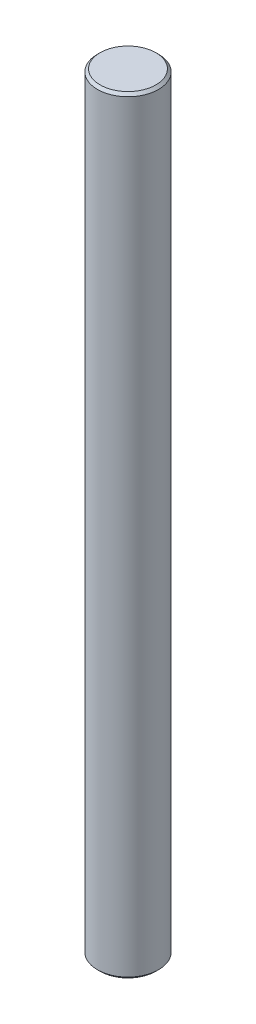
SolidWorks part; units mm, degrees
ref_plane "Front Plane" through (0, 0, 0) normal (0, 0, 1) x (1, 0, 0)
ref_plane "Top Plane" through (0, 0, 0) normal (0, 1, 0) x (1, 0, 0)
ref_plane "Right Plane" through (0, 0, 0) normal (1, 0, 0) x (0, 0, -1)
sketch "Sketch2" plane through (0, 0, 0) normal (0, 0, 1) x (1, 0, 0)
  line L1 (17.5, 440) -> (0, 440)
  line L2 (17.5, 440) -> (17.5, 0)
  line L3 (17.5, 0) -> (0, 0)
  line L4 (0, 440) -> (0, 0)
  line L5 (17.5, 440) -> (0, 0) construction
  line L6 (17.5, 0) -> (0, 440) construction
  point P0 (8.75, 220)
  dimension "D1" = 17.5
  dimension "D2" = 440
revolve "Revolve1" add sketch "Sketch2" angle 360 about L4
chamfer "Chamfer1" distance 1.5 angle 45 2 edges at (-17.5, 0, 0) (-17.5, 440, 0)
sketch "Sketch3" plane through (0, 0, 0) normal (0, -1, 0) x (1, 0, 0)
  circle A0 centre (0, 0) radius 0.5
  dimension "D1" = 1
extrude "Cut-Extrude1" cut sketch "Sketch3" against normal blind 3
ref_axis "Axis1" through (0, 1, 0) along (0, 1, 0)
